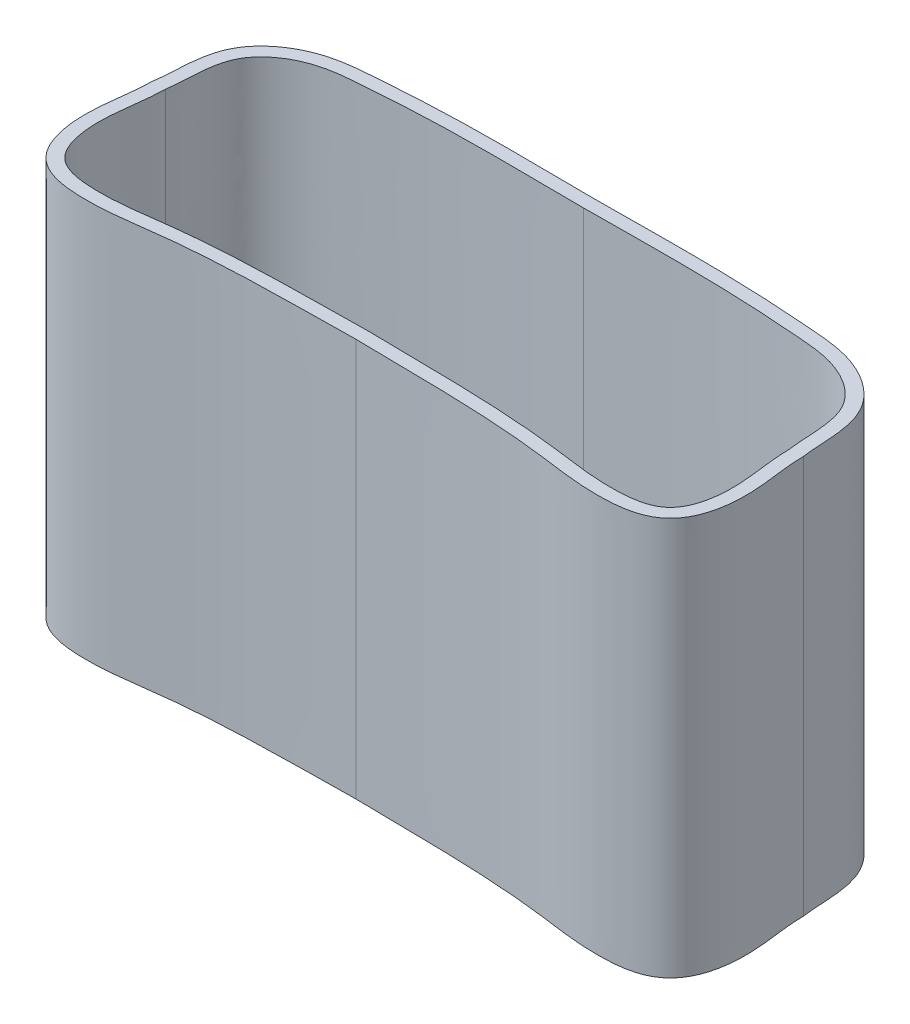
SolidWorks part; units mm, degrees
ref_plane "Ön Düzlem" through (0, 0, 0) normal (0, 0, 1) x (1, 0, 0)
ref_plane "Üst Düzlem" through (0, 0, 0) normal (0, 1, 0) x (1, 0, 0)
ref_plane "Sağ Düzlem" through (0, 0, 0) normal (1, 0, 0) x (0, 0, -1)
sketch "Çizim1" plane through (0, 0, 0) normal (0, 1, 0) x (1, 0, 0)
  line L0 (22.0273, 32.1041) -> (22.0273, -36.1576) construction
  line L1 (-24.9727, -4.0254) -> (69.0273, -4.0254) construction
  line L2 (-108.3091, -42.1463) -> (-63.9653, -42.1463) construction
  spline S0 degree 3 poles (-24.9727, -4.0254) (-24.5264, -1.0618) (-25.2539, 5.8819) (-17.6675, 10.7212) (-10.3172, 11.3557) (2.6606, 12.2457) (13.7373, 12.0216) (22.0273, 11.9677) knots 0 0 0 0 0.17039 0.314818 0.41507 0.5624 1 1 1 1
  spline S1 degree 3 poles (-24.9727, -4.0254) (-25.0191, -7.7747) (-26.4834, -12.7757) (-24.4521, -21.7474) (-15.657, -22.9109) (-1.1302, -20.3551) (12.6175, -20.4803) (22.0273, -20.317) knots 0 0 0 0 0.166073 0.272845 0.372685 0.539423 1 1 1 1
  spline S2 degree 3 poles (69.0273, -4.0254) (69.0736, -7.7747) (70.5379, -12.7757) (68.5066, -21.7474) (59.7115, -22.9109) (45.1847, -20.3551) (31.437, -20.4803) (22.0273, -20.317) knots 0 0 0 0 0.166073 0.272845 0.372685 0.539423 1 1 1 1
  spline S3 degree 3 poles (69.0273, -4.0254) (68.5809, -1.0618) (69.3084, 5.8819) (61.722, 10.7212) (54.3717, 11.3557) (41.3939, 12.2457) (30.3172, 12.0216) (22.0273, 11.9677) knots 0 0 0 0 0.17039 0.314818 0.41507 0.5624 1 1 1 1
  spline S4 degree 1 poles (-26.9709, -3.8633) (22.0273, 13.9678) knots 0 0 1 1 construction
  spline S5 degree 1 poles (71.0254, -3.8633) (22.0273, 13.9678) knots 0 0 1 1 construction
  spline S6 degree 1 poles (71.0254, -3.8633) (22.0273, -22.3173) knots 0 0 1 1 construction
  spline S7 degree 1 poles (-26.9709, -3.8633) (22.0273, -22.3173) knots 0 0 1 1 construction
  spline S8 degree 3 poles (-26.9709, -3.8633) (-26.9611, -3.7983) (-26.9405, -3.6635) (-26.9087, -3.4328) (-26.8558, -2.991) (-26.7738, -2.0607) (-26.6954, -0.5797) (-26.572, 1.3424) (-26.2988, 3.3542) (-25.7443, 5.4015) (-24.6869, 7.4087) (-23.232, 9.0593) (-20.959, 10.8533) (-17.6782, 12.3971) (-13.7233, 13.1079) (-10.1672, 13.348) (-6.5918, 13.6136) (-2.997, 13.8117) (1.7976, 13.9904) (7.7701, 14.0693) (14.9158, 14.0327) (19.6547, 13.9832) (22.0273, 13.9678) knots -0.002603 -0.002603 -0.002603 -0.002603 0.001312 0.005228 0.013059 0.028721 0.060045 0.091369 0.122694 0.154018 0.185342 0.216666 0.24799 0.310639 0.373287 0.435935 0.498584 0.561232 0.623881 0.749177 0.874474 0.999771 0.999771 0.999771 0.999771
  spline S9 degree 3 poles (22.0273, 13.9678) (24.3998, 13.9832) (29.1387, 14.0327) (36.2844, 14.0693) (42.2569, 13.9904) (47.0515, 13.8117) (50.6463, 13.6136) (54.2218, 13.348) (57.7778, 13.1079) (61.7327, 12.3971) (65.0135, 10.8533) (67.2865, 9.0593) (68.7414, 7.4087) (69.7988, 5.4015) (70.3533, 3.3542) (70.6265, 1.3424) (70.7499, -0.5797) (70.8283, -2.0607) (70.9103, -2.991) (70.9632, -3.4328) (70.995, -3.6635) (71.0156, -3.7983) (71.0254, -3.8633) knots -0.002603 -0.002603 -0.002603 -0.002603 0.122694 0.24799 0.373287 0.435935 0.498584 0.561232 0.623881 0.686529 0.749177 0.780501 0.811826 0.84315 0.874474 0.905798 0.937122 0.968447 0.984109 0.99194 0.995855 0.999771 0.999771 0.999771 0.999771
  spline S10 degree 3 poles (71.0254, -3.8633) (71.0274, -4.0288) (71.0325, -4.3644) (71.0572, -4.9986) (71.1298, -6.1076) (71.3682, -8.2903) (71.8135, -11.491) (71.8371, -15.1902) (71.2025, -18.3913) (70.3958, -20.3266) (69.3788, -21.7331) (68.0335, -22.9683) (66.0905, -23.8727) (63.7042, -24.3454) (61.3939, -24.4809) (59.2331, -24.4627) (56.4533, -24.2828) (53.1701, -23.8601) (49.4155, -23.3577) (44.2908, -22.8893) (37.7417, -22.5576) (31.1395, -22.4371) (25.8963, -22.3743) (23.3207, -22.3397) (22.0273, -22.3173) knots -0.002028 -0.002028 -0.002028 -0.002028 0.005796 0.01362 0.029268 0.060564 0.123155 0.185747 0.217042 0.248338 0.263986 0.279634 0.31093 0.342225 0.373521 0.404817 0.436113 0.498704 0.561296 0.623887 0.74907 0.874253 0.936845 0.999436 0.999436 0.999436 0.999436
  spline S11 degree 3 poles (22.0273, -22.3173) (20.7338, -22.3397) (18.1582, -22.3743) (12.9151, -22.4371) (6.3128, -22.5576) (-0.2363, -22.8893) (-5.361, -23.3577) (-9.1156, -23.8601) (-12.3988, -24.2828) (-15.1786, -24.4627) (-17.3394, -24.4809) (-19.6497, -24.3454) (-22.0359, -23.8727) (-23.979, -22.9683) (-25.3243, -21.7331) (-26.3413, -20.3266) (-27.1479, -18.3913) (-27.7826, -15.1902) (-27.7589, -11.491) (-27.3137, -8.2903) (-27.0753, -6.1076) (-27.0027, -4.9986) (-26.978, -4.3644) (-26.9729, -4.0288) (-26.9709, -3.8633) knots -0.002028 -0.002028 -0.002028 -0.002028 0.060564 0.123155 0.248338 0.373521 0.436113 0.498704 0.561296 0.592591 0.623887 0.655183 0.686479 0.717774 0.733422 0.74907 0.780366 0.811662 0.874253 0.936845 0.968141 0.983788 0.991612 0.999436 0.999436 0.999436 0.999436
  dimension "D1" = 47
extrude "Yükseklik-Ekstrüzyon1" add sketch "Çizim1" along normal blind 60
sketch "Çizim2" [suppressed] plane through (0, 60, 0) normal (0, 1, 0) x (1, 0, 0)
  line L1 (22.0615, -20.317) -> (22.0615, -18.317)
ref_plane "Düzlem1" [suppressed] through (0, 0, 20.317) normal (0, 0, -1) x (-1, 0, 0)
sketch "Çizim3" [suppressed] plane through (0, 0, 20.317) normal (0, 0, -1) x (-1, 0, 0)
  line L2 (-22.0615, 60) -> (-22.0615, 0) construction
  circle A0 centre (-22.0615, 45) radius 1.5
  circle A1 centre (-22.0615, 55) radius 1.5
  dimension "D1" = 10
  dimension "D3" = 3
extrude "Kes-Ekstrüzyon1" [suppressed] cut sketch "Çizim3" along normal blind 10 and the other way blind 10
sketch "Çizim4" plane through (0, 0, 0) normal (0, -1, 0) x (1, 0, 0)
  spline S34 degree 3 poles (419.7463, -1944.9233) (-33.0762, 32.4932) (-27.4513, 7.3613) (-26.9087, 3.4328) (-26.8558, 2.991) (-26.7738, 2.0607) (-26.6954, 0.5797) (-26.572, -1.3424) (-26.2988, -3.3542) (-25.7443, -5.4015) (-24.6869, -7.4087) (-23.232, -9.0593) (-20.959, -10.8533) (-17.6782, -12.3971) (-13.7233, -13.1079) (-10.1672, -13.348) (-6.5918, -13.6136) (-2.997, -13.8117) (1.7976, -13.9904) (7.7701, -14.0693) (124.0005, -13.4754) (223.5857, 1.482) (1271.8302, -1567.8799) knots -0.253665 -0.253665 -0.253665 -0.253665 0.001312 0.005228 0.013059 0.028721 0.060045 0.091369 0.122694 0.154018 0.185342 0.216666 0.24799 0.310639 0.373287 0.435935 0.498584 0.561232 0.623881 0.749177 0.874474 6.738005 6.738005 6.738005 6.738005 only from (-26.9709, 3.8633) to (22.0273, -13.9678)
  spline S35 degree 3 poles (-1227.7643, -1567.8629) (-179.5305, 1.4819) (-79.9456, -13.4754) (36.2844, -14.0693) (42.2569, -13.9904) (47.0515, -13.8117) (50.6463, -13.6136) (54.2218, -13.348) (57.7778, -13.1079) (61.7327, -12.3971) (65.0135, -10.8533) (67.2865, -9.0593) (68.7414, -7.4087) (69.7988, -5.4015) (70.3533, -3.3542) (70.6265, -1.3424) (70.7499, 0.5797) (70.8283, 2.0607) (70.9103, 2.991) (70.9632, 3.4328) (71.5058, 7.3614) (77.1308, 32.4935) (-375.7011, -1944.9639) knots -5.740816 -5.740816 -5.740816 -5.740816 0.122694 0.24799 0.373287 0.435935 0.498584 0.561232 0.623881 0.686529 0.749177 0.780501 0.811826 0.84315 0.874474 0.905798 0.937122 0.968447 0.984109 0.99194 0.995855 1.250835 1.250835 1.250835 1.250835 only from (22.0273, -13.9678) to (71.0254, 3.8633)
  spline S36 degree 3 poles (-297.4617, 1969.5332) (78.5217, -38.0593) (70.6275, -6.0607) (71.0572, 4.9986) (71.1298, 6.1076) (71.3682, 8.2903) (71.8135, 11.491) (71.8371, 15.1902) (71.2025, 18.3913) (70.3958, 20.3266) (69.3788, 21.7331) (68.0335, 22.9683) (66.0905, 23.8727) (63.7042, 24.3454) (61.3939, 24.4809) (59.2331, 24.4627) (56.4533, 24.2828) (53.1701, 23.8601) (49.4155, 23.3577) (44.2908, 22.8893) (37.7417, 22.5576) (31.1395, 22.4371) (-35.1147, 21.6437) (-71.6741, 18.9569) (-1924.3242, -437.2353) knots -0.516484 -0.516484 -0.516484 -0.516484 0.005796 0.01362 0.029268 0.060564 0.123155 0.185747 0.217042 0.248338 0.263986 0.279634 0.31093 0.342225 0.373521 0.404817 0.436113 0.498704 0.561296 0.623887 0.74907 0.874253 0.936845 3.91279 3.91279 3.91279 3.91279 only from (71.0254, 3.8633) to (22.0273, 22.3173)
  spline S37 degree 3 poles (1968.3847, -437.2368) (115.7287, 18.9569) (79.1692, 21.6437) (12.9151, 22.4371) (6.3128, 22.5576) (-0.2363, 22.8893) (-5.361, 23.3577) (-9.1156, 23.8601) (-12.3988, 24.2828) (-15.1786, 24.4627) (-17.3394, 24.4809) (-19.6497, 24.3454) (-22.0359, 23.8727) (-23.979, 22.9683) (-25.3243, 21.7331) (-26.3413, 20.3266) (-27.1479, 18.3913) (-27.7826, 15.1902) (-27.7589, 11.491) (-27.3137, 8.2903) (-27.0753, 6.1076) (-27.0027, 4.9986) (-26.573, -6.0603) (-34.4666, -38.057) (341.4755, 1969.3158) knots -2.915385 -2.915385 -2.915385 -2.915385 0.060564 0.123155 0.248338 0.373521 0.436113 0.498704 0.561296 0.592591 0.623887 0.655183 0.686479 0.717774 0.733422 0.74907 0.780366 0.811662 0.874253 0.936845 0.968141 0.983788 0.991612 1.513873 1.513873 1.513873 1.513873 only from (22.0273, 22.3173) to (-26.9709, 3.8633)
  spline S38 degree 3 poles (-26.9709, 3.8633) (-26.9611, 3.7983) (-26.9405, 3.6635) (-26.9087, 3.4328) (-26.8558, 2.991) (-26.7738, 2.0607) (-26.6954, 0.5797) (-26.572, -1.3424) (-26.2988, -3.3542) (-25.7443, -5.4015) (-24.6869, -7.4087) (-23.232, -9.0593) (-20.959, -10.8533) (-17.6782, -12.3971) (-13.7233, -13.1079) (-10.1672, -13.348) (-6.5918, -13.6136) (-2.997, -13.8117) (1.7976, -13.9904) (7.7701, -14.0693) (14.9158, -14.0327) (19.6547, -13.9832) (22.0273, -13.9678) knots -0.002603 -0.002603 -0.002603 -0.002603 0.001312 0.005228 0.013059 0.028721 0.060045 0.091369 0.122694 0.154018 0.185342 0.216666 0.24799 0.310639 0.373287 0.435935 0.498584 0.561232 0.623881 0.749177 0.874474 0.999771 0.999771 0.999771 0.999771
  spline S39 degree 3 poles (22.0273, -13.9678) (24.3998, -13.9832) (29.1387, -14.0327) (36.2844, -14.0693) (42.2569, -13.9904) (47.0515, -13.8117) (50.6463, -13.6136) (54.2218, -13.348) (57.7778, -13.1079) (61.7327, -12.3971) (65.0135, -10.8533) (67.2865, -9.0593) (68.7414, -7.4087) (69.7988, -5.4015) (70.3533, -3.3542) (70.6265, -1.3424) (70.7499, 0.5797) (70.8283, 2.0607) (70.9103, 2.991) (70.9632, 3.4328) (70.995, 3.6635) (71.0156, 3.7983) (71.0254, 3.8633) knots -0.002603 -0.002603 -0.002603 -0.002603 0.122694 0.24799 0.373287 0.435935 0.498584 0.561232 0.623881 0.686529 0.749177 0.780501 0.811826 0.84315 0.874474 0.905798 0.937122 0.968447 0.984109 0.99194 0.995855 0.999771 0.999771 0.999771 0.999771
  spline S40 degree 3 poles (71.0254, 3.8633) (71.0274, 4.0288) (71.0325, 4.3644) (71.0572, 4.9986) (71.1298, 6.1076) (71.3682, 8.2903) (71.8135, 11.491) (71.8371, 15.1902) (71.2025, 18.3913) (70.3958, 20.3266) (69.3788, 21.7331) (68.0335, 22.9683) (66.0905, 23.8727) (63.7042, 24.3454) (61.3939, 24.4809) (59.2331, 24.4627) (56.4533, 24.2828) (53.1701, 23.8601) (49.4155, 23.3577) (44.2908, 22.8893) (37.7417, 22.5576) (31.1395, 22.4371) (25.8963, 22.3743) (23.3207, 22.3397) (22.0273, 22.3173) knots -0.002028 -0.002028 -0.002028 -0.002028 0.005796 0.01362 0.029268 0.060564 0.123155 0.185747 0.217042 0.248338 0.263986 0.279634 0.31093 0.342225 0.373521 0.404817 0.436113 0.498704 0.561296 0.623887 0.74907 0.874253 0.936845 0.999436 0.999436 0.999436 0.999436
  spline S41 degree 3 poles (22.0273, 22.3173) (20.7338, 22.3397) (18.1582, 22.3743) (12.9151, 22.4371) (6.3128, 22.5576) (-0.2363, 22.8893) (-5.361, 23.3577) (-9.1156, 23.8601) (-12.3988, 24.2828) (-15.1786, 24.4627) (-17.3394, 24.4809) (-19.6497, 24.3454) (-22.0359, 23.8727) (-23.979, 22.9683) (-25.3243, 21.7331) (-26.3413, 20.3266) (-27.1479, 18.3913) (-27.7826, 15.1902) (-27.7589, 11.491) (-27.3137, 8.2903) (-27.0753, 6.1076) (-27.0027, 4.9986) (-26.978, 4.3644) (-26.9729, 4.0288) (-26.9709, 3.8633) knots -0.002028 -0.002028 -0.002028 -0.002028 0.060564 0.123155 0.248338 0.373521 0.436113 0.498704 0.561296 0.592591 0.623887 0.655183 0.686479 0.717774 0.733422 0.74907 0.780366 0.811662 0.874253 0.936845 0.968141 0.983788 0.991612 0.999436 0.999436 0.999436 0.999436
  dimension "D1" = 0
extrude "Yükseklik-Ekstrüzyon2" add sketch "Çizim4" against normal blind 3
